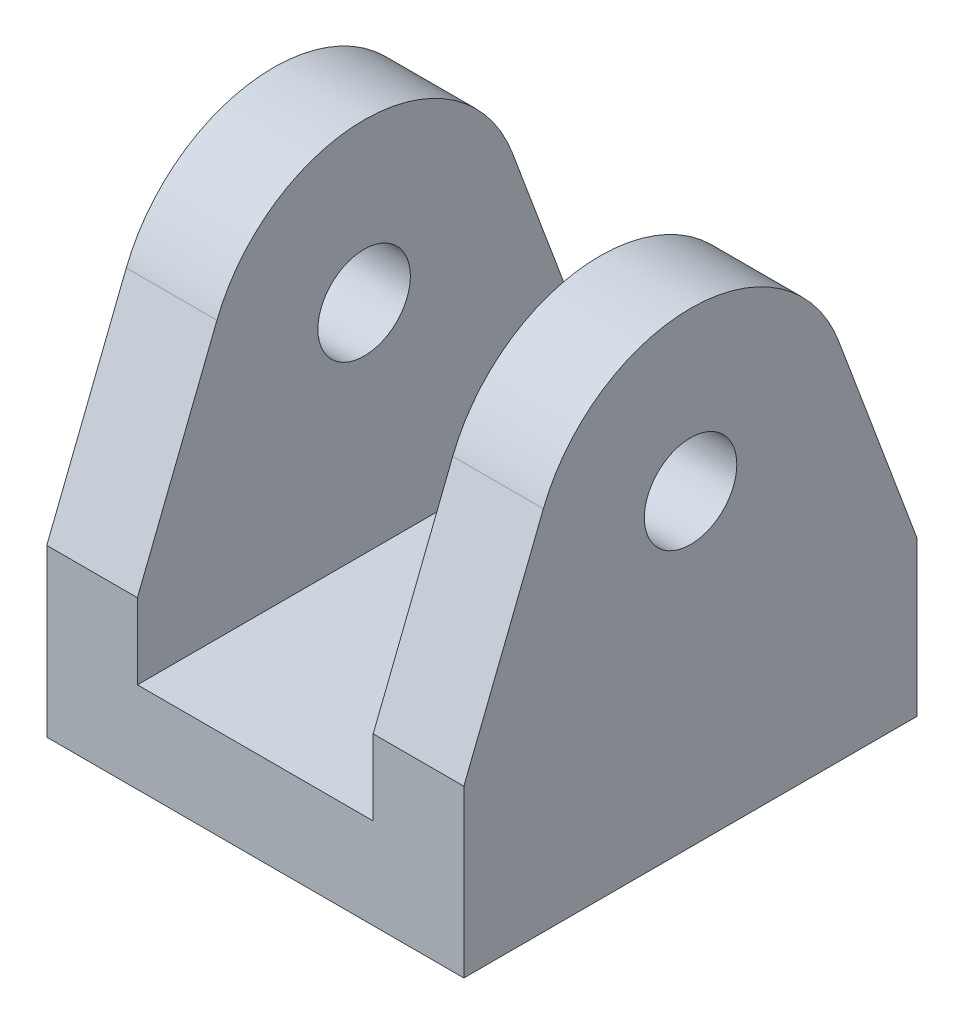
SolidWorks part; units mm, degrees
ref_plane "Front Plane" through (0, 0, 0) normal (0, 0, 1) x (1, 0, 0)
ref_plane "Top Plane" through (0, 0, 0) normal (0, 1, 0) x (1, 0, 0)
ref_plane "Right Plane" through (0, 0, 0) normal (1, 0, 0) x (0, 0, -1)
sketch "Sketch1" plane through (0, 0, 0) normal (0, 0, 1) x (1, 0, 0)
  line L0 (0, 0) -> (0, 5) construction
  line L1 (-6.5, 5) -> (6.5, 5)
  line L2 (6.5, 5) -> (6.5, 25.7299)
  line L3 (6.5, 25.7299) -> (11.5, 25.7299)
  line L4 (11.5, 25.7299) -> (11.5, 0)
  line L5 (11.5, 0) -> (-11.5, 0)
  line L6 (-11.5, 25.7299) -> (-11.5, 0)
  line L7 (-6.5, 25.7299) -> (-11.5, 25.7299)
  line L8 (-6.5, 5) -> (-6.5, 25.7299)
  dimension "D1" = 5
  dimension "D2" = 5
  dimension "D3" = 20.7299
  dimension "D4" = 13
extrude "Boss-Extrude1" add sketch "Sketch1" along normal mid plane 25
sketch "Sketch2" plane through (0, 0, 0) normal (1, 0, 0) x (0, 0, -1)
  line L0 (-12.5, 9.1594) -> (-8.1153, 20.2178)
  line L1 (-12.5, 0) -> (-12.5, 25.7299) construction
  line L2 (8.1779, 20.0551) -> (12.5, 8.4856)
  line L3 (12.5, 0) -> (12.5, 25.7299) construction
  line L4 (0, 17) -> (0, 0) construction
  line L8 (12.5, 0) -> (12.5, 25.7299)
  line L9 (12.5, 25.7299) -> (-12.5, 25.7299)
  line L10 (-12.5, 25.7299) -> (-12.5, 0)
  line L11 (-12.5, 0) -> (12.5, 0)
  line L12 (12.5, 0) -> (12.5, 25.7299)
  line L13 (12.5, 25.7299) -> (-12.5, 25.7299)
  line L14 (-12.5, 25.7299) -> (-12.5, 0)
  line L15 (-12.5, 0) -> (12.5, 0)
  arc A0 (-8.1153, 20.2178) -> (8.1779, 20.0551) centre (0, 17) cw
  circle A1 centre (0, 17) radius 2.55
  dimension "D3" = 5.1
  dimension "D2" = 17
  dimension "D1" = 0
extrude "Cut-Extrude1" cut sketch "Sketch2" against normal mid plane 43 contours L0 A0 L13 L14 | A1 | L13 A0 L2 L12 region at (0, 20.6572, 9.7733) region at (0, 20.4671, -9.8034) region at (0, 17, 0)
